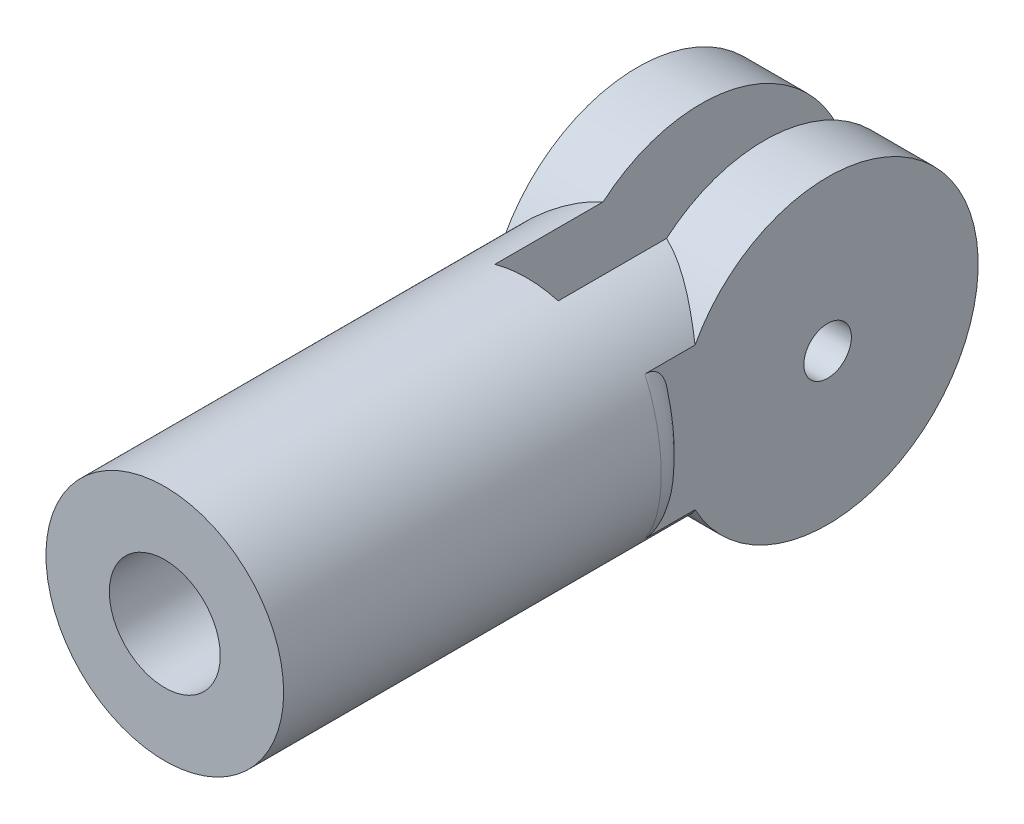
SolidWorks part; units mm, degrees
ref_plane "Спереди" through (0, 0, 0) normal (0, 0, 1) x (1, 0, 0)
ref_plane "Сверху" through (0, 0, 0) normal (0, 1, 0) x (1, 0, 0)
ref_plane "Справа" through (0, 0, 0) normal (1, 0, 0) x (0, 0, -1)
sketch "Sketch1" plane through (0, 0, 0) normal (0, 0, 1) x (1, 0, 0)
  circle A0 centre (0, 0) radius 3.5
  circle A1 centre (0, 0) radius 7.5
  dimension "D1" = 7
  dimension "D2" = 4
extrude "Boss-Extrude1" add sketch "Sketch1" along normal blind 30
sketch "Sketch2" plane through (0, 0, 0) normal (1, 0, 0) x (0, 0, -1)
  circle A0 centre (5.831, 0) radius 9.5
  dimension "D1" = 19
extrude "Boss-Extrude2" add sketch "Sketch2" along normal mid plane 12
sketch "Sketch4" plane through (-6, 0, 0) normal (-1, 0, 0) x (0, 0, 1)
  circle A0 centre (-5.831, 0) radius 1.5
  dimension "D1" = 3
extrude "Cut-Extrude1" cut sketch "Sketch4" against normal mid plane 34
sketch "Sketch5" plane through (6, 0, 0) normal (1, 0, 0) x (0, 0, -1)
  circle A0 centre (5.831, 0) radius 10
extrude "Cut-Extrude2" cut sketch "Sketch5" along normal blind 31
sketch "Sketch6" plane through (-6, 0, 0) normal (-1, 0, 0) x (0, 0, 1)
  circle A0 centre (-5.831, 0) radius 10
extrude "Cut-Extrude3" cut sketch "Sketch6" along normal blind 25
fillet "Fillet3" radius 2 2 edges at (7.4962, 0.2384, 4.1662) (-7.4962, -0.2384, 4.1662)
sketch "Sketch7" plane through (0, 0, 0) normal (1, 0, 0) x (0, 0, -1)
  line L1 (18.831, -13) -> (-7.169, -13)
  line L2 (18.831, -13) -> (18.831, 13)
  line L3 (18.831, 13) -> (-7.169, 13)
  line L4 (-7.169, -13) -> (-7.169, 13)
  line L5 (18.831, -13) -> (-7.169, 13) construction
  line L6 (18.831, 13) -> (-7.169, -13) construction
  point P0 (5.831, 0)
  dimension "D1" = 26
extrude "Cut-Extrude4" cut sketch "Sketch7" against normal mid plane 4
